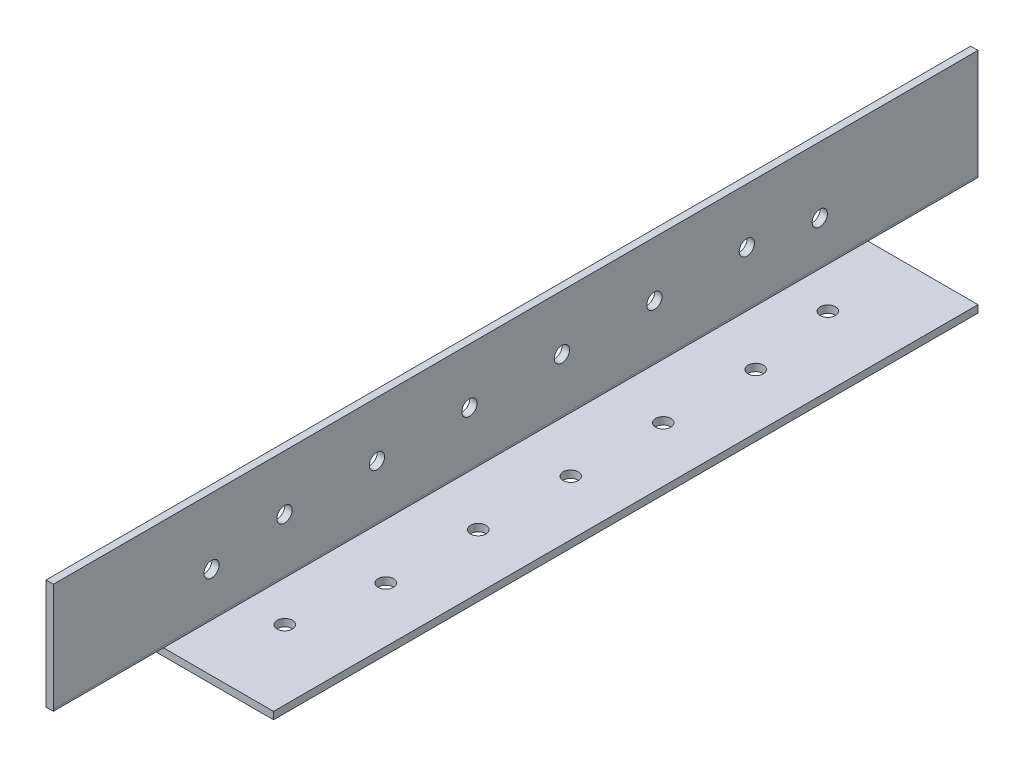
SolidWorks part; units mm, degrees
ref_plane "Front Plane" through (0, 0, 0) normal (0, 0, 1) x (1, 0, 0)
ref_plane "Top Plane" through (0, 0, 0) normal (0, 1, 0) x (1, 0, 0)
ref_plane "Right Plane" through (0, 0, 0) normal (1, 0, 0) x (0, 0, -1)
sketch "Sketch1" plane through (0, 0, 0) normal (0, 0, 1) x (1, 0, 0)
  line L0 (0, 25.4) -> (0, 0) construction
  line L1 (0, 0) -> (25.4, 0) construction
  line L2 (25.4, 0) -> (25.4, 1.5875) construction
  line L3 (25.4, 1.5875) -> (1.5875, 1.5875) construction
  line L4 (1.5875, 1.5875) -> (1.5875, 25.4) construction
  line L6 (1.5875, 25.4) -> (0, 25.4) construction
  arc A0 (1.5875, 1.8415) -> (1.8415, 1.5875) centre (1.8415, 1.8415) ccw construction
  point P4 (0, 0)
  dimension "Inside Corner Radius" = 0.254
  dimension "Outside Height" = 25.4
  dimension "Inside Height" = 23.8125
  dimension "Outside Width" = 25.4
  dimension "Inside Width" = 23.8125
  dimension "Wall Thickness" = 1.5875
  dimension "Shape" = 90
sketch "Sketch2" plane through (0, 0, 0) normal (1, 0, 0) x (0, 0, -1)
  line L0 (1219.2, 0) -> (-1219.2, 0) construction
  line L1 (-1219.2, 25.4) -> (-1219.2, 0) construction
  line L2 (1219.2, 25.4) -> (1219.2, 0) construction
  point P0 (-1189.99, 0)
  point P4 (0, 0)
  point P6 (1189.99, 0)
  dimension "D1" = 29.21
  dimension "D2" = 29.21
  dimension "D3" = 25.4
  dimension "Length" = 2438.4
sketch "Sketch3" plane through (0, 0, 0) normal (0, 0, 1) x (1, 0, 0)
  line L0 (1.5875, 25.4) -> (0, 25.4)
  line L1 (0, 25.4) -> (0, 0)
  line L2 (0, 0) -> (25.4, 0)
  line L3 (25.4, 0) -> (25.4, 1.5875)
  line L4 (25.4, 1.5875) -> (1.5875, 1.5875)
  line L5 (1.5875, 1.5875) -> (1.5875, 25.4)
extrude "Boss-Extrude1" add sketch "Sketch3" along normal mid plane 2438.4
fillet "Fillet1" radius 0.254 1 edges at (1.5875, 1.5875, 0)
sketch "Sketch4" plane through (0, 0, 0) normal (-1, 0, 0) x (0, 0, 1)
  line L0 (1219.2, 25.4) -> (1219.2, 0) construction
  line L1 (-1219.2, 0) -> (1019.2, 0)
  line L2 (-1219.2, 0) -> (-1219.2, 74.9453)
  line L3 (-1219.2, 74.9453) -> (1019.2, 74.9453)
  line L4 (1019.2, 0) -> (1019.2, 74.9453)
  dimension "D1" = 200
extrude "Cut-Extrude1" cut sketch "Sketch4" against normal blind 60
sketch "Sketch8" plane through (0, 1.5875, 0) normal (0, 1, 0) x (1, 0, 0)
  line L0 (25.4, -1119.2) -> (1.5875, -1119.2) construction
  line L1 (25.4, -1219.2) -> (1.587, -1219.2)
  line L2 (25.4, -1219.2) -> (25.4, -1195.387)
  line L3 (25.4, -1195.387) -> (1.587, -1195.387)
  line L4 (1.587, -1219.2) -> (1.587, -1195.387)
  line L5 (25.4, -1219.2) -> (25.4, -1019.2) construction
  line L6 (1.5875, -1219.2) -> (1.5875, -1019.2) construction
  line L7 (25.4, -1043.013) -> (1.587, -1043.013)
  line L8 (1.587, -1019.2) -> (1.587, -1043.013)
  line L9 (25.4, -1019.2) -> (1.587, -1019.2)
  line L10 (25.4, -1019.2) -> (25.4, -1043.013)
  dimension "D1" = 23.813
extrude "Cut-Extrude6" cut sketch "Sketch8" against normal blind 28.313
sketch "Sketch9" plane through (0, 0, 1019.2) normal (0, 0, -1) x (-1, 0, 0)
  line L0 (-1.8415, 1.5875) -> (-1.587, 1.5875)
  line L1 (-1.587, 1.5875) -> (-1.5875, 1.9903)
  line L2 (-1.5875, 1.8415) -> (-1.5875, 25.4) construction
  line L3 (-1.5875, 1.9903) -> (-1.8415, 1.9903)
  line L4 (-1.8415, 1.9903) -> (-1.8415, 1.5875)
extrude "Cut-Extrude7" cut sketch "Sketch9" against normal blind 228.313
sketch "Sketch10" plane through (0, 0, 0) normal (-1, 0, 0) x (0, 0, 1)
  line L0 (1119.2, 25.4) -> (1119.2, 0) construction
  line L1 (1219.2, 25.4) -> (1195.387, 25.4)
  line L2 (1219.2, 25.4) -> (1219.2, 1.587)
  line L3 (1219.2, 1.587) -> (1195.387, 1.587)
  line L4 (1195.387, 25.4) -> (1195.387, 1.587)
  line L5 (1195.387, 1.587) -> (1219.2, 1.587)
  line L6 (1195.387, 1.587) -> (1195.387, 0)
  line L7 (1195.387, 0) -> (1219.2, 0)
  line L8 (1219.2, 1.587) -> (1219.2, 0)
  line L9 (1219.2, 25.4) -> (1019.2, 25.4) construction
  line L10 (1219.2, 0) -> (1019.2, 0) construction
  line L11 (1043.013, 0) -> (1019.2, 0)
  line L12 (1019.2, 1.587) -> (1019.2, 0)
  line L13 (1043.013, 1.587) -> (1019.2, 1.587)
  line L14 (1043.013, 1.587) -> (1043.013, 0)
  line M11 (1019.2, 0) -> (1219.2, 0)
  line M12 (1219.2, 0) -> (1219.2, 25.4)
  dimension "D1" = 23.813
  dimension "D2" = 23.813
extrude "Cut-Extrude8" cut sketch "Sketch10" against normal blind 228.313 contours L3 L6 M11 M12 | L11 L12 L13 L14 region at (0, 0.7935, 1207.2935)
sketch "Sketch14" plane through (0, 1.5875, 0) normal (0, 1, 0) x (1, 0, 0)
  line L0 (25.4, -1159.2003) -> (1.5875, -1159.2003) construction
  line L1 (25.4, -1195.387) -> (25.4, -1043.013) construction
  line L2 (1.5875, -1219.2) -> (1.5875, -1019.2) construction
  line L3 (10.3759, -1177.925) -> (10.3759, -1159.2003) construction
  line L4 (25.4, -1079.2003) -> (1.5875, -1079.2003) construction
  line L5 (10.3759, -1060.4755) -> (10.3759, -1079.2003) construction
  circle A0 centre (10.3759, -1177.925) radius 1.65
  circle A1 centre (10.3759, -1060.4755) radius 1.65
  circle A2 centre (13.4937, -1079.2003) radius 1.65
  circle A3 centre (13.4938, -1099.2003) radius 1.65
  circle A4 centre (13.4938, -1119.2003) radius 1.65
  circle A5 centre (13.4938, -1139.2003) radius 1.65
  circle A6 centre (13.4938, -1159.2003) radius 1.65
  point P18 (0, 0)
  dimension "D1" = 3.3
  dimension "D3" = 20
  dimension "D2" = 5
extrude "Cut-Extrude11" cut sketch "Sketch14" against normal blind 60
sketch "Sketch15" plane through (1.5875, 0, 0) normal (1, 0, 0) x (0, 0, -1)
  line L0 (-1069.2, 1.5875) -> (-1069.2, 25.4) construction
  line L1 (-1195.387, 1.5875) -> (-1043.013, 1.5875) construction
  line L2 (-1219.2, 25.4) -> (-1019.2, 25.4) construction
  line L3 (-1053.4212, 11.1125) -> (-1069.2, 11.1125) construction
  line L4 (-1184.9788, 11.1125) -> (-1184.9788, 25.4) construction
  line L5 (-1169.2, 13.4937) -> (-1184.9788, 13.4937) construction
  circle A0 centre (-1184.9788, 11.1125) radius 1.65
  circle A1 centre (-1053.4212, 11.1125) radius 1.65
  circle A2 centre (-1069.2, 13.4938) radius 1.65
  circle A3 centre (-1089.2, 13.4938) radius 1.65
  circle A4 centre (-1109.2, 13.4938) radius 1.65
  circle A5 centre (-1129.2, 13.4938) radius 1.65
  circle A6 centre (-1149.2, 13.4938) radius 1.65
  circle A7 centre (-1169.2, 13.4937) radius 1.65
  dimension "D1" = 3.3
  dimension "D3" = 20
  dimension "D2" = 6
extrude "Cut-Extrude12" cut sketch "Sketch15" against normal blind 60
equation "\"D1@Boss-Extrude1\"=\"Length@Sketch2\""
equation "\"D1@Sketch2\" = \"Outside Width@Sketch1\" * 1.15"
equation "\"D2@Sketch2\"=\"D1@Sketch2\""
equation "\"D1@Fillet1\"=\"Inside Corner Radius@Sketch1\""
equation "\"D3@Sketch2\"=\"Outside Height@Sketch1\""
